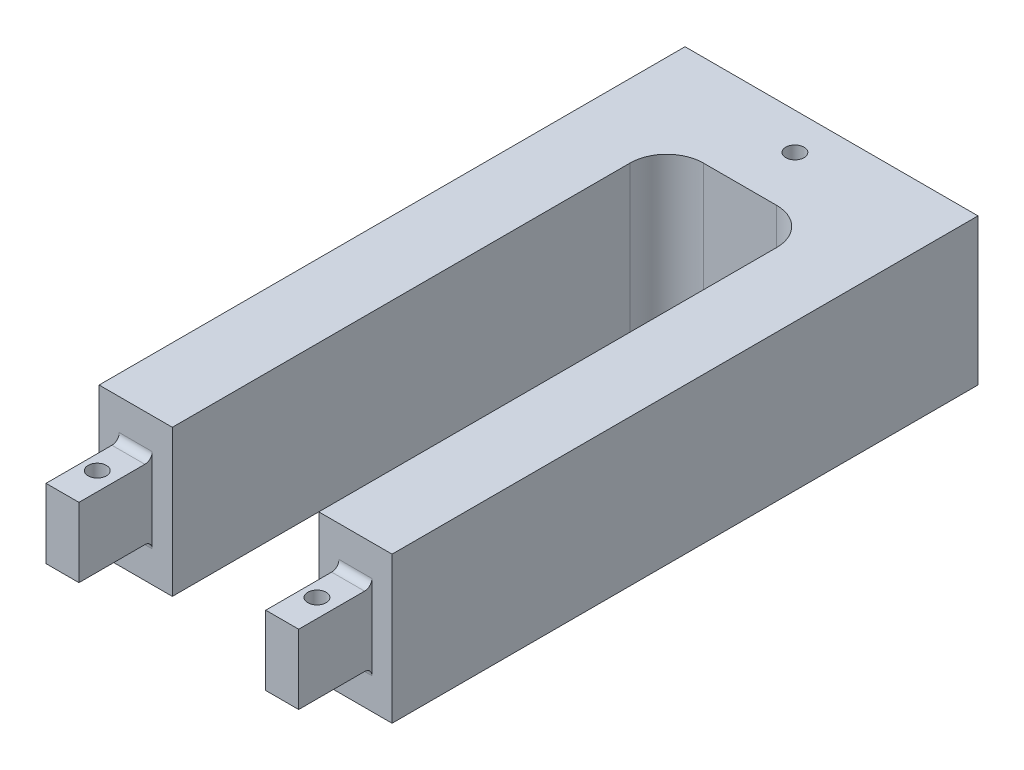
SolidWorks part; units mm, degrees
ref_plane "Front Plane" through (0, 0, 0) normal (0, 0, 1) x (1, 0, 0)
ref_plane "Top Plane" through (0, 0, 0) normal (0, 1, 0) x (1, 0, 0)
ref_plane "Right Plane" through (0, 0, 0) normal (1, 0, 0) x (0, 0, -1)
sketch "Sketch1" plane through (0, 0, 0) normal (0, 1, 0) x (1, 0, 0)
  line L0 (-59.1713, -17.6011) -> (-59.1713, 185.5989)
  line L1 (-59.1713, 185.5989) -> (42.4287, 185.5989)
  line L2 (42.4287, 185.5989) -> (42.4287, -17.6011)
  line L3 (42.4287, -17.6011) -> (17.0287, -17.6011)
  line L4 (17.0287, -17.6011) -> (17.0287, 160.1989)
  line L5 (17.0287, 160.1989) -> (-33.7713, 160.1989)
  line L6 (-33.7713, 160.1989) -> (-33.7713, -17.6011)
  line L7 (-33.7713, -17.6011) -> (-59.1713, -17.6011)
  dimension "D1" = 203.2
  dimension "D2" = 101.6
  dimension "D3" = 50.8
  dimension "D4" = 177.8
extrude "Boss-Extrude1" add sketch "Sketch1" along normal blind 50.8
sketch "Sketch2" plane through (0, 0, 17.6011) normal (0, 0, 1) x (1, 0, 0)
  line L0 (-59.1713, 50.8) -> (-33.7713, 50.8) construction
  line L1 (-52.1863, 13.335) -> (-40.7563, 13.335)
  line L2 (-52.1863, 13.335) -> (-52.1863, 37.465)
  line L3 (-52.1863, 37.465) -> (-40.7563, 37.465)
  line L4 (-40.7563, 13.335) -> (-40.7563, 37.465)
  line L5 (-52.1863, 13.335) -> (-40.7563, 37.465) construction
  line L6 (-52.1863, 37.465) -> (-40.7563, 13.335) construction
  line L7 (-59.1713, 50.8) -> (-59.1713, 0) construction
  line L8 (24.0137, 13.335) -> (24.0137, 37.465)
  line L9 (24.0137, 37.465) -> (35.4437, 37.465)
  line L10 (35.4437, 13.335) -> (35.4437, 37.465)
  line L11 (24.0137, 13.335) -> (35.4437, 13.335)
  line L12 (42.4287, 50.8) -> (42.4287, 0) construction
  point P0 (-46.4713, 25.4)
  dimension "D1" = 24.13
  dimension "D2" = 11.43
  dimension "D3" = 25.4
  dimension "D4" = 6.985
  dimension "D6" = 6.985
  dimension "D5" = 2
extrude "Boss-Extrude2" add sketch "Sketch2" along normal blind 25.4
fillet "Fillet3" radius 2.54 4 edges at (29.7287, 13.335, 17.6011) (-46.4713, 13.335, 17.6011) (29.7287, 37.465, 17.6011) (-46.4713, 37.465, 17.6011)
sketch "Sketch3" plane through (0, 37.465, 0) normal (0, 1, 0) x (1, 0, 0)
  line L0 (-59.1713, -17.6011) -> (-33.7713, -17.6011) construction
  line L1 (-40.7563, -43.0011) -> (-40.7563, -20.1411) construction
  line L2 (17.0287, -17.6011) -> (42.4287, -17.6011) construction
  line L3 (35.4437, -43.0011) -> (35.4437, -20.1411) construction
  circle A0 centre (-47.1063, -30.3011) radius 3.175
  circle A1 centre (29.0937, -30.3011) radius 3.175
  dimension "D1" = 6.35
  dimension "D2" = 12.7
  dimension "D3" = 6.35
  dimension "D4" = 12.7
  dimension "D5" = 6.35
extrude "Cut-Extrude1" cut sketch "Sketch3" against normal through all
sketch "Sketch4" plane through (0, 0, -185.5989) normal (0, 0, -1) x (-1, 0, 0)
  line L0 (-42.4287, 50.8) -> (59.1713, 50.8) construction
  line L1 (-29.7287, 32.004) -> (46.4713, 32.004)
  line L2 (-29.7287, 32.004) -> (-29.7287, 18.796)
  line L3 (-29.7287, 18.796) -> (46.4713, 18.796)
  line L4 (46.4713, 32.004) -> (46.4713, 18.796)
  line L5 (59.1713, 50.8) -> (59.1713, 0) construction
  line L7 (-4.5827, 9.906) -> (21.3253, 9.906)
  line L8 (-4.5827, 9.906) -> (-4.5827, 40.894)
  line L9 (-4.5827, 40.894) -> (21.3253, 40.894)
  line L10 (21.3253, 9.906) -> (21.3253, 40.894)
  line L11 (-4.5827, 9.906) -> (21.3253, 40.894) construction
  line L12 (-4.5827, 40.894) -> (21.3253, 9.906) construction
  point P4 (-29.7287, 25.4)
  point P7 (8.3713, 18.796)
  point P10 (8.3713, 25.4)
  point P15 (8.3713, 32.004)
  dimension "D1" = 13.208
  dimension "D2" = 76.2
  dimension "D3" = 25.4
  dimension "D4" = 50.8
  dimension "D5" = 30.988
  dimension "D6" = 0
  dimension "D7" = 0
  dimension "D8" = 25.908
extrude "Cut-Extrude2" cut sketch "Sketch4" against normal blind 25.4 contours L3 L8 L1 L2 | L3 L10 L1 L8 | L1 L10 L9 L8 | L10 L3 L4 L1 | L7 L10 L3 L8 region at (17.1557, 25.4, -185.5989) region at (-8.3713, 36.449, -185.5989) region at (-8.3713, 25.4, -185.5989) region at (-33.8983, 25.4, -185.5989) region at (-8.3713, 14.351, -185.5989)
chamfer "Chamfer1" distance 8.89 angle 45 4 edges at (-21.3253, 32.004, -172.8989) (-21.3253, 18.796, -172.8989) (4.5827, 18.796, -172.8989) (4.5827, 32.004, -172.8989)
sketch "Sketch5" plane through (0, 0, 0) normal (0, -1, 0) x (1, 0, 0)
  line L1 (-33.7713, -160.1989) -> (17.0287, -160.1989) construction
  line L2 (42.4287, 17.6011) -> (42.4287, -185.5989) construction
  circle A0 centre (-8.3713, -172.8989) radius 3.175
  dimension "D1" = 6.35
  dimension "D2" = 12.7
  dimension "D3" = 50.8
extrude "Cut-Extrude3" cut sketch "Sketch5" against normal through all
sketch "Sketch7" plane through (0, 0, -160.1989) normal (0, 0, 1) x (1, 0, 0)
  line L1 (-33.7713, 50.8) -> (17.0287, 50.8)
  line L2 (-33.7713, 50.8) -> (-33.7713, 0)
  line L3 (-33.7713, 0) -> (17.0287, 0)
  line L4 (17.0287, 50.8) -> (17.0287, 0)
extrude "Boss-Extrude4" add sketch "Sketch7" along normal blind 6.35
fillet "Fillet4" radius 12.7 2 edges at (17.0287, 25.4, -153.8489) (-33.7713, 25.4, -153.8489)
